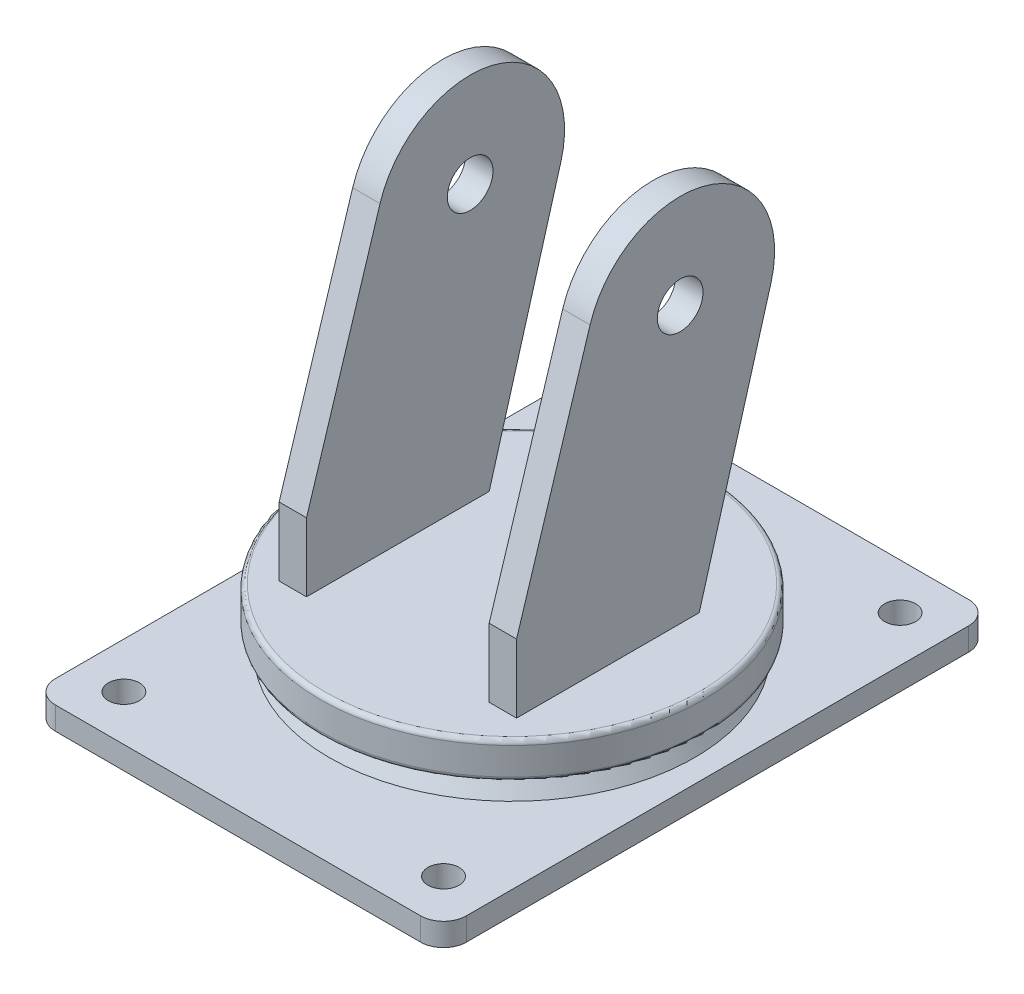
SolidWorks part; units mm, degrees
ref_plane "前视基准面" through (0, 0, 0) normal (0, 0, 1) x (1, 0, 0)
ref_plane "上视基准面" through (0, 0, 0) normal (0, 1, 0) x (1, 0, 0)
ref_plane "右视基准面" through (0, 0, 0) normal (1, 0, 0) x (0, 0, -1)
sketch "草图1" plane through (0, 0, 0) normal (0, 1, 0) x (1, 0, 0)
  line L1 (-45, 60) -> (45, 60)
  line L2 (-45, 60) -> (-45, -60)
  line L3 (-45, -60) -> (45, -60)
  line L4 (45, 60) -> (45, -60)
  line L5 (-45, 60) -> (45, -60) construction
  line L6 (-45, -60) -> (45, 60) construction
  point P0 (0, 0)
  dimension "D1" = 90
  dimension "D2" = 120
extrude "凸台-拉伸1" add sketch "草图1" along normal blind 5
fillet "圆角3" radius 5 4 edges at (45, 2.5, 60) (-45, 2.5, 60) (-45, 2.5, -60) (45, 2.5, -60)
sketch "草图2" plane through (0, 5, 0) normal (0, 1, 0) x (1, 0, 0)
  line L0 (0, 0) -> (-20, 0) construction
  line L2 (-20, 0) -> (-20, -40)
  line L3 (-20, -40) -> (-30, -40)
  line L4 (-20, 0) -> (-20, 40)
  line L5 (-20, 40) -> (-30, 40)
  line L6 (-30, 40) -> (-30, -40)
  line L7 (0, 0) -> (0, 13.1624) construction
  line L8 (20, 0) -> (20, -40)
  line L9 (20, -40) -> (30, -40)
  line L10 (30, 40) -> (30, -40)
  line L11 (20, 40) -> (30, 40)
  line L12 (20, 0) -> (20, 40)
  dimension "D1" = 20
  dimension "D2" = 40
  dimension "D3" = 10
  dimension "D4" = 40
sketch "草图11" plane through (0, 5, 0) normal (0, 1, 0) x (1, 0, 0)
  line L0 (0, 0) -> (-35, 50)
  line L1 (0, 0) -> (0, 50)
  line L2 (0, 50) -> (-35, 50)
  line L3 (40, 60) -> (-40, 60) construction
  line L4 (-45, 55) -> (-45, -55) construction
  dimension "D1" = 50
  dimension "D2" = 35
  dimension "D3" = 10
  dimension "D4" = 10
hole_wizard "M8 螺纹孔1" positions "草图16" profile "草图17" tap size "M8" standard "GB"
sketch "草图16" plane through (0, 5, 0) normal (0, 1, 0) x (1, 0, 0)
  point P0 (-35, 50)
sketch "草图17" plane through (-35, 5, -50) normal (1, 0, 0) x (0, 0, 1)
  line L0 (0, 0) -> (0, 21.7929)
  line L1 (0, 21.7929) -> (3.4, 19.75)
  line L2 (3.4, 19.75) -> (3.4, 0)
  line L5 (3.4, 0) -> (0, 0)
  line L10 (0, 21.7929) -> (-3.4, 19.75) construction
  line L11 (0, -6.35) -> (0, 107.95) construction
  dimension "螺纹孔钻头直径" = 6.8
  dimension "螺纹孔钻头深度" = 19.75
  dimension "导头角度" = 118
cosmetic thread "孔螺纹线6" parameters "D1"=16, "D2"=8
mirror "镜向4" about plane through (0, 0, 0) normal (1, 0, 0) of "M8 螺纹孔1"
cosmetic thread "孔螺纹线7" parameters "D1"=16, "D2"=8
mirror "镜向5" about plane through (0, 0, 0) normal (0, 0, 1) of "M8 螺纹孔1", "镜向4"
cosmetic thread "孔螺纹线8" parameters "D1"=16, "D2"=8
cosmetic thread "孔螺纹线9" parameters "D1"=16, "D2"=8
sketch "草图21" plane through (0, 0, 0) normal (0, -1, 0) x (1, 0, 0)
  circle A0 centre (0, 0) radius 17.5
  dimension "D1" = 35
extrude "切除-拉伸1" cut sketch "草图21" against normal blind 2
fillet "圆角4" radius 0.5 1 edges at (0, 0, -17.5)
sketch "草图22" plane through (0, 2, 0) normal (0, -1, 0) x (1, 0, 0)
  circle A0 centre (0, 0) radius 16.5
  dimension "D1" = 33
extrude "凸台-拉伸2" add sketch "草图22" along normal blind 2
fillet "圆角5" radius 2 1 edges at (0, 0, -16.5)
fillet "圆角6" radius 0.5 1 edges at (0, 2, -17.5)
sketch "草图26" plane through (0, 0, 0) normal (1, 0, 0) x (0, 0, -1)
  line L0 (0, 5) -> (-40, 5)
  line L1 (40, 5) -> (-40, 5) construction
  line L2 (-55, 5) -> (55, 5) construction
  line L5 (-37, 10) -> (-40, 5)
  line L6 (-37, 10) -> (0, 10)
  line L7 (0, 10) -> (0, 5)
  dimension "D1" = 40
  dimension "D2" = 5
revolve "旋转1" add sketch "草图26" angle 360 about L7
sketch "草图27" plane through (0, 10, 0) normal (0, 1, 0) x (1, 0, 0)
  circle A0 centre (0, 0) radius 42
  dimension "D1" = 84
extrude "凸台-拉伸4" add sketch "草图27" along normal blind 8
ref_plane "基准面1" through (20, 0, 0) normal (1, 0, 0) x (0, 0, -1)
sketch "草图30" plane through (20, 0, 0) normal (1, 0, 0) x (0, 0, -1)
  line L0 (0, 18) -> (15, 18)
  line L1 (42, 18) -> (-42, 18) construction
  line L2 (0, 18) -> (-25, 18)
  line L3 (-25, 18) -> (-25, 33)
  line L6 (-25, 33) -> (-8.901, 84.5384)
  line L9 (15, 18) -> (30.7121, 72.6597)
  arc A0 (30.7121, 72.6597) -> (-8.901, 84.5384) centre (10.8376, 78.3727) ccw
  dimension "D1" = 15
  dimension "D2" = 25
  dimension "D3" = 15
extrude "凸台-拉伸5" add sketch "草图30" along normal blind 6
mirror "镜向6" about plane through (0, 0, 0) normal (1, 0, 0) of "凸台-拉伸5"
sketch "草图31" plane through (26, 0, 0) normal (1, 0, 0) x (0, 0, -1)
  circle A0 centre (10.8376, 78.3727) radius 5
  dimension "D1" = 10
extrude "切除-拉伸2" cut sketch "草图31" against normal blind 85
fillet "圆角7" radius 1 1 edges at (0, 10, 42)
fillet "圆角8" radius 1 1 edges at (0, 18, 42)
